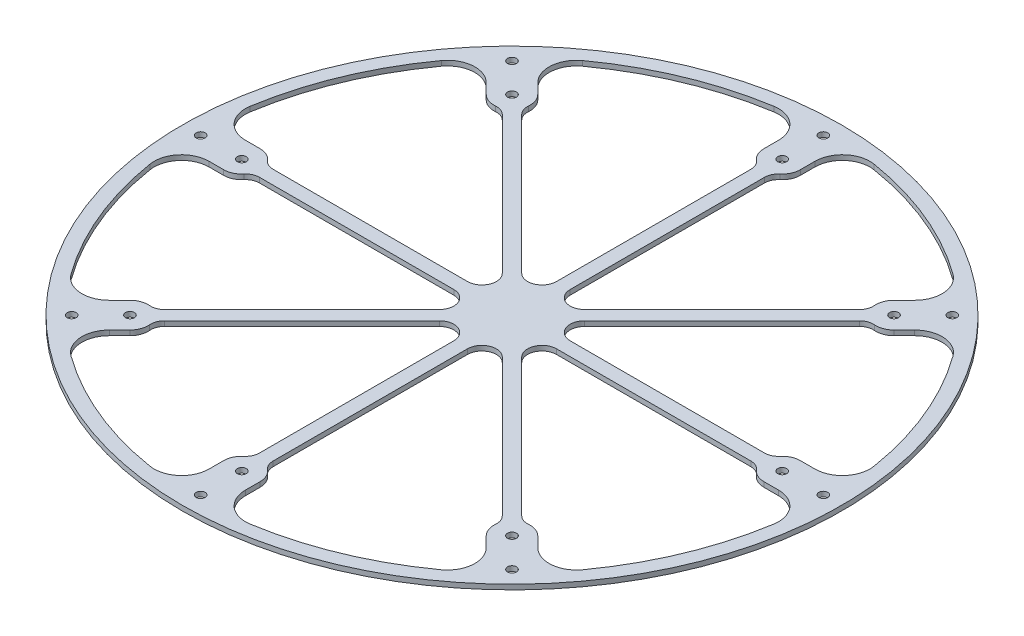
SolidWorks part; units mm, degrees
material "Thornel Mat VMA"
ref_plane "Front Plane" through (0, 0, 0) normal (0, 0, 1) x (1, 0, 0)
ref_plane "Top Plane" through (0, 0, 0) normal (0, 1, 0) x (1, 0, 0)
ref_plane "Right Plane" through (0, 0, 0) normal (1, 0, 0) x (0, 0, -1)
sketch "Sketch1" plane through (0, 0, 0) normal (0, 1, 0) x (1, 0, 0)
  line L0 (0, 0) -> (-152.4, 0) construction
  line L1 (0, 0) -> (-124.9299, 0) construction
  circle A0 centre (0, 0) radius 152.4
  circle A1 centre (-143.9799, 0) radius 2.0701
  circle A2 centre (-124.9299, 0) radius 2.0701
  circle A3 centre (-143.9799, 0) radius 8.4201 construction
  circle A4 centre (-101.8092, 101.8092) radius 8.4201 construction
  circle A5 centre (-101.8092, 101.8092) radius 2.0701
  circle A6 centre (-88.3388, 88.3388) radius 2.0701
  circle A7 centre (0, 143.9799) radius 8.4201 construction
  circle A8 centre (0, 143.9799) radius 2.0701
  circle A9 centre (0, 124.9299) radius 2.0701
  circle A10 centre (101.8092, 101.8092) radius 8.4201 construction
  circle A11 centre (101.8092, 101.8092) radius 2.0701
  circle A12 centre (88.3388, 88.3388) radius 2.0701
  circle A13 centre (143.9799, 0) radius 8.4201 construction
  circle A14 centre (143.9799, 0) radius 2.0701
  circle A15 centre (124.9299, 0) radius 2.0701
  circle A16 centre (101.8092, -101.8092) radius 8.4201 construction
  circle A17 centre (101.8092, -101.8092) radius 2.0701
  circle A18 centre (88.3388, -88.3388) radius 2.0701
  circle A19 centre (0, -143.9799) radius 8.4201 construction
  circle A20 centre (0, -143.9799) radius 2.0701
  circle A21 centre (0, -124.9299) radius 2.0701
  circle A22 centre (-101.8092, -101.8092) radius 8.4201 construction
  circle A23 centre (-101.8092, -101.8092) radius 2.0701
  circle A24 centre (-88.3388, -88.3388) radius 2.0701
  dimension "D1" = 304.8
  dimension "D2" = 4.1402
  dimension "D4" = 6.35
  dimension "D3" = 19.05
  dimension "D6" = 124.9299
  dimension "D5" = 8
extrude "Boss-Extrude1" add sketch "Sketch1" along normal blind 2.286
sketch "Sketch2" plane through (0, 2.286, 0) normal (0, 1, 0) x (1, 0, 0)
  line L0 (0, 0) -> (0, -152.4) construction
  line L1 (0, 0) -> (107.7631, -107.7631) construction
  line L2 (8.4201, -124.9299) -> (8.4201, -143.9799)
  line L3 (0, 0) -> (58.321, -140.7992) construction
  line L4 (11.0369, -15.527) -> (94.0497, -98.5398)
  line L5 (82.3849, -94.2927) -> (95.8553, -107.7631)
  line L6 (3.175, -18.7836) -> (3.175, -136.1813)
  circle A0 centre (0, 0) radius 152.4 construction
  circle A1 centre (101.8092, -101.8092) radius 2.0701 construction
  circle A2 centre (88.3388, -88.3388) radius 2.0701 construction
  circle A3 centre (0, -124.9299) radius 2.0701 construction
  circle A4 centre (0, -143.9799) radius 2.0701 construction
  circle A5 centre (0, 0) radius 152.4
  circle A6 centre (101.8092, -101.8092) radius 2.0701
  circle A7 centre (88.3388, -88.3388) radius 2.0701
  circle A8 centre (0, -124.9299) radius 2.0701
  circle A9 centre (0, -143.9799) radius 2.0701
  circle A10 centre (0, -124.9299) radius 8.4201
  circle A11 centre (0, -143.9799) radius 8.4201
  circle A12 centre (101.8092, -101.8092) radius 8.4201
  circle A13 centre (88.3388, -88.3388) radius 8.4201
  circle A14 centre (0, 0) radius 146.05
  circle A15 centre (0, 0) radius 19.05
  arc A16 (8.4201, -131.6669) -> (23.1315, -144.2066) centre (21.1201, -131.6669) ccw
  arc A17 (87.1486, -99.0564) -> (85.613, -118.3259) centre (78.1684, -108.0367) cw
  arc A18 (14.5548, -19.0449) -> (3.175, -23.7586) centre (9.8411, -23.7586) ccw
  dimension "D2" = 38.1
  dimension "D4" = 25.4
  dimension "D3" = 3.175
  dimension "D5" = 22.5
  dimension "D1" = 6.35
extrude "Cut-Extrude1" cut sketch "Sketch2" against normal through all contours L4 A18 L6 A10 L2 A16 A14 A17 L5 A13 region at (37.1176, 2.286, 89.6098)
pattern_circular "CirPattern1" count 8 every 45 about axis through (0, 0, 0) along (0, 1, 0) of "Cut-Extrude1"
fillet "Fillet1" radius 6.35 16 edges at (3.175, 1.143, -117.1313) (-3.175, 1.143, -117.1313) (-80.5793, 1.143, -85.0694) (-85.0694, 1.143, -80.5793) (-117.1313, 1.143, -3.175) (-117.1313, 1.143, 3.175) (-80.5793, 1.143, 85.0694) (-85.0694, 1.143, 80.5793) (-3.175, 1.143, 117.1313) (3.175, 1.143, 117.1313) (85.0694, 1.143, 80.5793) (80.5793, 1.143, 85.0694) (117.1313, 1.143, 3.175) (117.1313, 1.143, -3.175) (80.5793, 1.143, -85.0694) (85.0694, 1.143, -80.5793)
